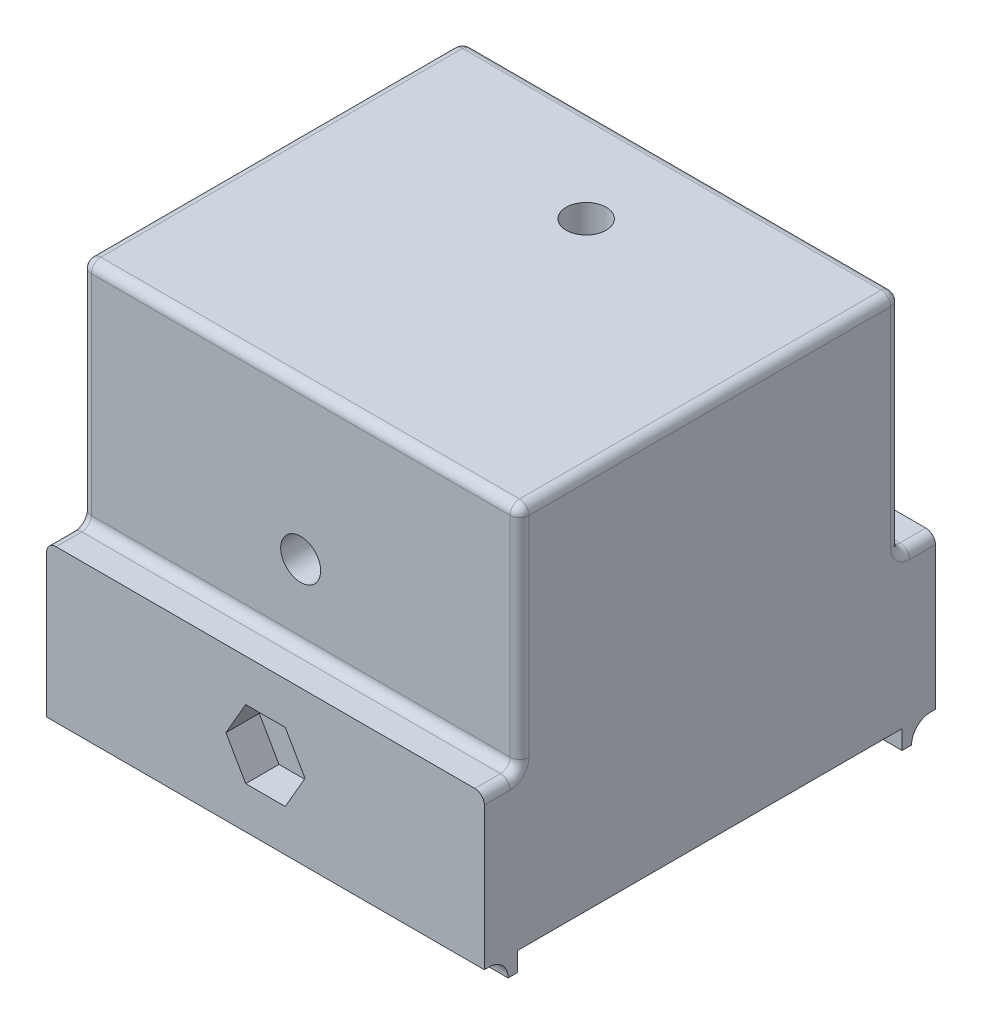
SolidWorks part; units mm, degrees
ref_plane "Front Plane" through (0, 0, 0) normal (0, 0, 1) x (1, 0, 0)
ref_plane "Top Plane" through (0, 0, 0) normal (0, 1, 0) x (1, 0, 0)
ref_plane "Right Plane" through (0, 0, 0) normal (1, 0, 0) x (0, 0, -1)
sketch "Sketch1" plane through (0, 0, 0) normal (0, 1, 0) x (1, 0, 0)
  line L1 (-23, 20) -> (23, 20)
  line L2 (-23, 20) -> (-23, -20)
  line L3 (-23, -20) -> (23, -20)
  line L4 (23, 20) -> (23, -20)
  line L5 (-23, 20) -> (23, -20) construction
  line L6 (-23, -20) -> (23, 20) construction
  point P4 (0, 0)
  dimension "D1" = 40
  dimension "D2" = 46
extrude "Boss-Extrude1" add sketch "Sketch1" along normal blind 40
sketch "Sketch2" plane through (0, 0, 0) normal (0, -1, 0) x (1, 0, 0)
  line L1 (-23, 23.7) -> (23, 23.7)
  line L2 (-23, 23.7) -> (-23, 20)
  line L3 (-23, 20) -> (23, 20)
  line L4 (23, 23.7) -> (23, 20)
  line L5 (-23, 23.7) -> (23, 20) construction
  line L6 (-23, 20) -> (23, 23.7) construction
  line L7 (-23, -20) -> (23, -20)
  line L8 (-23, -20) -> (-23, -23.7)
  line L9 (-23, -23.7) -> (23, -23.7)
  line L10 (23, -20) -> (23, -23.7)
  line L11 (-23, -20) -> (23, -23.7) construction
  line L12 (-23, -23.7) -> (23, -20) construction
  point P4 (0, 21.85)
  point P12 (0, -21.85)
  dimension "D1" = 3.7
  dimension "D2" = 3.7
extrude "Boss-Extrude2" add sketch "Sketch2" against normal blind 16
sketch "Sketch3" plane through (0, 0, -23.7) normal (0, 0, -1) x (-1, 0, 0)
  line L0 (-23, 16) -> (23, 0) construction
  line L1 (23, 16) -> (-23, 0) construction
  line L3 (2.0785, 11.6) -> (-2.0785, 11.6)
  line L4 (-2.0785, 11.6) -> (-4.1569, 8)
  line L5 (-4.1569, 8) -> (-2.0785, 4.4)
  line L6 (-2.0785, 4.4) -> (2.0785, 4.4)
  line L7 (2.0785, 4.4) -> (4.1569, 8)
  line L8 (4.1569, 8) -> (2.0785, 11.6)
  circle A1 centre (0, 8) radius 3.6 construction
  dimension "D1" = 7.2
sketch "Sketch5" plane through (0, 0, 0) normal (0, -1, 0) x (1, 0, 0)
  line L0 (-23, -23.7) -> (-23, 23.7) construction
  line L1 (-20, 17) -> (20, 17)
  line L2 (-20, 17) -> (-20, -17)
  line L3 (-20, -17) -> (20, -17)
  line L4 (20, 17) -> (20, -17)
  line L5 (-20, 17) -> (20, -17) construction
  line L6 (-20, -17) -> (20, 17) construction
  line L8 (23, -20) -> (-23, -20) construction
  line L9 (23, -20) -> (-23, -20) construction
  point P4 (0, 0)
  dimension "D1" = 3
  dimension "D2" = 3
extrude "Cut-Extrude3" cut sketch "Sketch5" against normal blind 37
fillet "Fillet1" radius 1 14 edges at (0, 16, 20) (0, 16, -20) (23, 16, 21.85) (23, 28, 20) (23, 28, -20) (23, 16, -21.85) (-23, 16, -21.85) (-23, 28, -20) (-23, 28, 20) (-23, 16, 21.85) (0, 40, -20) (23, 40, 0) (0, 40, 20) (-23, 40, 0)
fillet "Fillet2" radius 1 8 edges at (0, 37, 17) (20, 37, 0) (0, 37, -17) (-20, 37, 0) (-20, 18.5, -17) (20, 18.5, -17) (-20, 18.5, 17) (20, 18.5, 17)
sketch "Sketch8" plane through (0, 0, 0) normal (0, -1, 0) x (1, 0, 0)
  line L0 (-23, 20) -> (23, 20) construction
  line L1 (-23, 20) -> (23, 20) construction
  line L2 (0, 0) -> (0, 20) construction
  line L8 (-23, -23.7) -> (23, -23.7)
  line L13 (23, -23.7) -> (23, 23.7)
  line L14 (23, 23.7) -> (-23, 23.7)
  line L15 (-23, 23.7) -> (-23, -23.7)
  line L16 (-23, -23.7) -> (23, -23.7)
  line L21 (23, -23.7) -> (23, 23.7)
  line L22 (23, 23.7) -> (-23, 23.7)
  line L23 (-23, 23.7) -> (-23, -23.7)
  circle A0 centre (0, 0) radius 20 construction
  dimension "D2" = 20
  dimension "D1" = 0
extrude "Cut-Extrude6" cut sketch "Sketch3" against normal blind 3.5
sketch "Measure Shearing Area" plane through (0, 0, -23.7) normal (0, 0, -1) x (-1, 0, 0)
  line L0 (-4.1569, 8) -> (-4.1569, 0)
  line L1 (23, 0) -> (-23, 0) construction
  line L2 (-4.1569, 0) -> (4.1569, 0)
  line L3 (4.1569, 0) -> (4.1569, 8)
  line L4 (4.1569, 8) -> (2.0785, 4.4)
  line L5 (2.0785, 4.4) -> (-2.0785, 4.4)
  line L6 (-2.0785, 4.4) -> (-4.1569, 8)
mirror "Mirror2" about plane through (0, 0, 0) normal (0, 0, 1) of "Cut-Extrude6"
sketch "Sketch9" plane through (0, 0, 0) normal (0, -1, 0) x (1, 0, 0)
  line L0 (-23, -23.7) -> (-23, 23.7) construction
  line L1 (-23, 21.2) -> (23, 21.2)
  line L2 (-23, 21.2) -> (-23, 20.2)
  line L3 (-23, 20.2) -> (23, 20.2)
  line L4 (23, 21.2) -> (23, 20.2)
  line L5 (-23, 21.2) -> (23, 20.2) construction
  line L6 (-23, 20.2) -> (23, 21.2) construction
  line L7 (23, 23.7) -> (23, -23.7) construction
  line L8 (-23, 0) -> (23, 0) construction
  line L9 (-23, -20.2) -> (23, -20.2)
  line L10 (23, -21.2) -> (23, -20.2)
  line L11 (-23, -21.2) -> (23, -21.2)
  line L12 (-23, -21.2) -> (-23, -20.2)
  point P4 (0, 20.7)
  dimension "D1" = 20.2
  dimension "D2" = 1
extrude "Boss-Extrude3" add sketch "Sketch9" along normal blind 2
sketch "Sketch12" plane through (0, 0, 20) normal (0, 0, 1) x (1, 0, 0)
  line L0 (-23, 28) -> (23, 28) construction
  line L1 (0, 0) -> (0, 40) construction
  line L2 (-22, 40) -> (22, 40) construction
  line L3 (-23, 17) -> (-23, 39) construction
  line L4 (23, 39) -> (23, 17) construction
  line L6 (-22, 21.9) -> (22, 21.9) construction
  line L7 (-22, 39) -> (-22, 17) construction
  line L8 (22, 17) -> (22, 39) construction
  line L9 (22, 16) -> (-22, 16) construction
  circle A1 centre (0, 24) radius 2.1
  dimension "D1" = 4.2
  dimension "D2" = 4
  dimension "D3" = 5.9
sketch "Sketch13" plane through (0, 40, 0) normal (0, 1, 0) x (1, 0, 0)
  line L0 (-23, 0) -> (23, 0) construction
  line L1 (0, 23.7) -> (0, -23.7) construction
  line L2 (23, 19) -> (23, -19) construction
  line L3 (-23, -19) -> (-23, 19) construction
  line L4 (-22, 23.7) -> (22, 23.7) construction
  line L5 (22, -23.7) -> (-22, -23.7) construction
  circle A1 centre (0, 10) radius 2.1
  dimension "D1" = 4.2
  dimension "D2" = 10
extrude "Cut-Extrude7" cut sketch "Sketch12" against normal up to next
extrude "Cut-Extrude8" cut sketch "Sketch13" against normal up to next
fillet "Fillet3" radius 2 2 edges at (0, 0, 21.2) (0, 0, -21.2)
